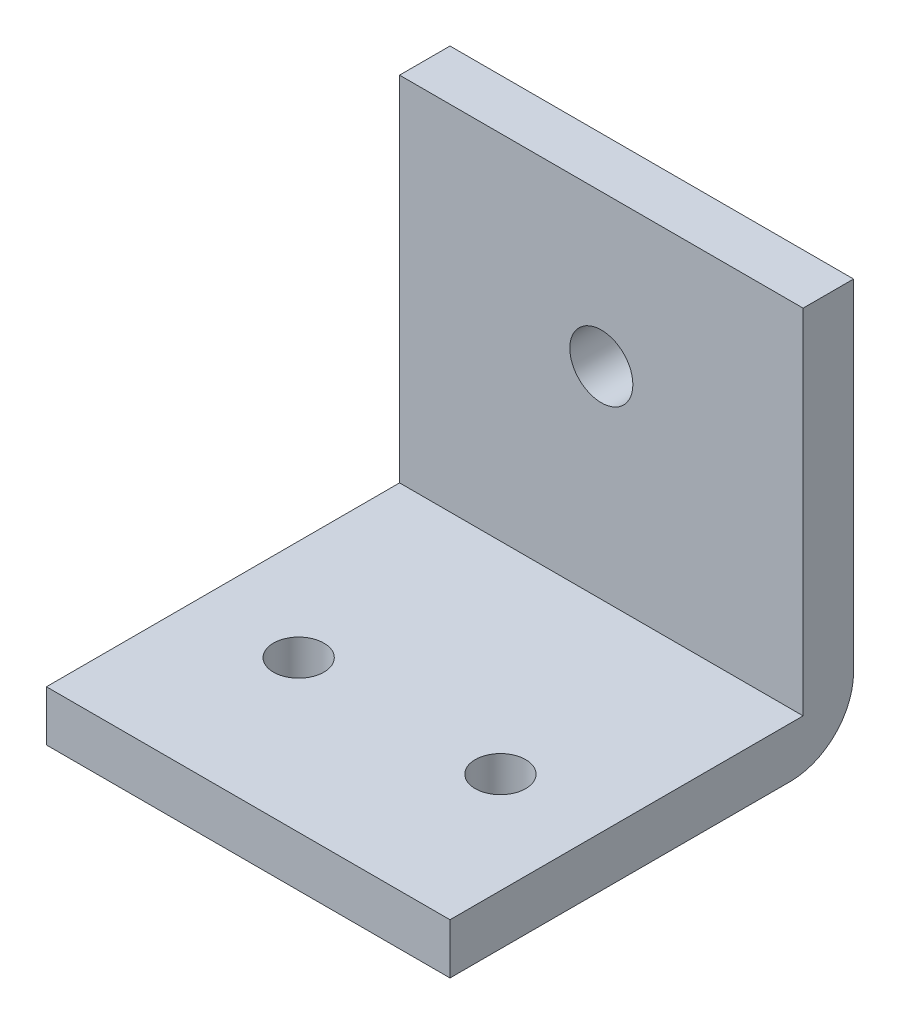
SolidWorks part; units mm, degrees
ref_plane "Front Plane" through (0, 0, 0) normal (0, 0, 1) x (1, 0, 0)
ref_plane "Top Plane" through (0, 0, 0) normal (0, 1, 0) x (1, 0, 0)
ref_plane "Right Plane" through (0, 0, 0) normal (1, 0, 0) x (0, 0, -1)
sketch "Sketch1" plane through (0, 0, 0) normal (0, 0, 1) x (1, 0, 0)
  line L0 (20, 25) -> (20, 40) construction
  line L1 (0, 0) -> (40, 0)
  line L2 (0, 0) -> (0, 40)
  line L3 (0, 40) -> (40, 40)
  line L4 (40, 0) -> (40, 40)
  line L6 (0, 0) -> (40, 0)
  line L7 (0, 0) -> (0, 5)
  line L8 (0, 5) -> (40, 5)
  line L9 (40, 0) -> (40, 5)
  circle A0 centre (20, 25) radius 3.125
  dimension "D3" = 6.25
  dimension "D4" = 15
  dimension "D1" = 40
  dimension "D2" = 40
  dimension "D5" = 5
extrude "Boss-Extrude1" add sketch "Sketch1" along normal blind 5 contours A0 L3 L2 L8 L4 region at (0.5315, 22.5, 0)
extrude "Boss-Extrude2" add sketch "Sketch1<3>" along normal blind 40 contours L8 L2 L1 L4 region at (20, 2.5, 0)
sketch "Sketch1<3>" plane through (0, 0, 0) normal (0, 0, 1) x (1, 0, 0) same geometry as "Sketch1"
fillet "Fillet1" radius 6.25 1 edges at (20, 0, 0)
sketch "Sketch2" plane through (0, 5, 0) normal (0, 1, 0) x (1, 0, 0)
  line L0 (7.5, -25) -> (32.5, -25) construction
  line L1 (0, -40) -> (0, -5) construction
  line L3 (0, -40) -> (40, -40) construction
  circle A0 centre (10, -25) radius 2.5
  circle A1 centre (30, -25) radius 2.5
  dimension "D1" = 5
  dimension "D2" = 10
  dimension "D3" = 15
extrude "Cut-Extrude1" cut sketch "Sketch2" against normal through all
